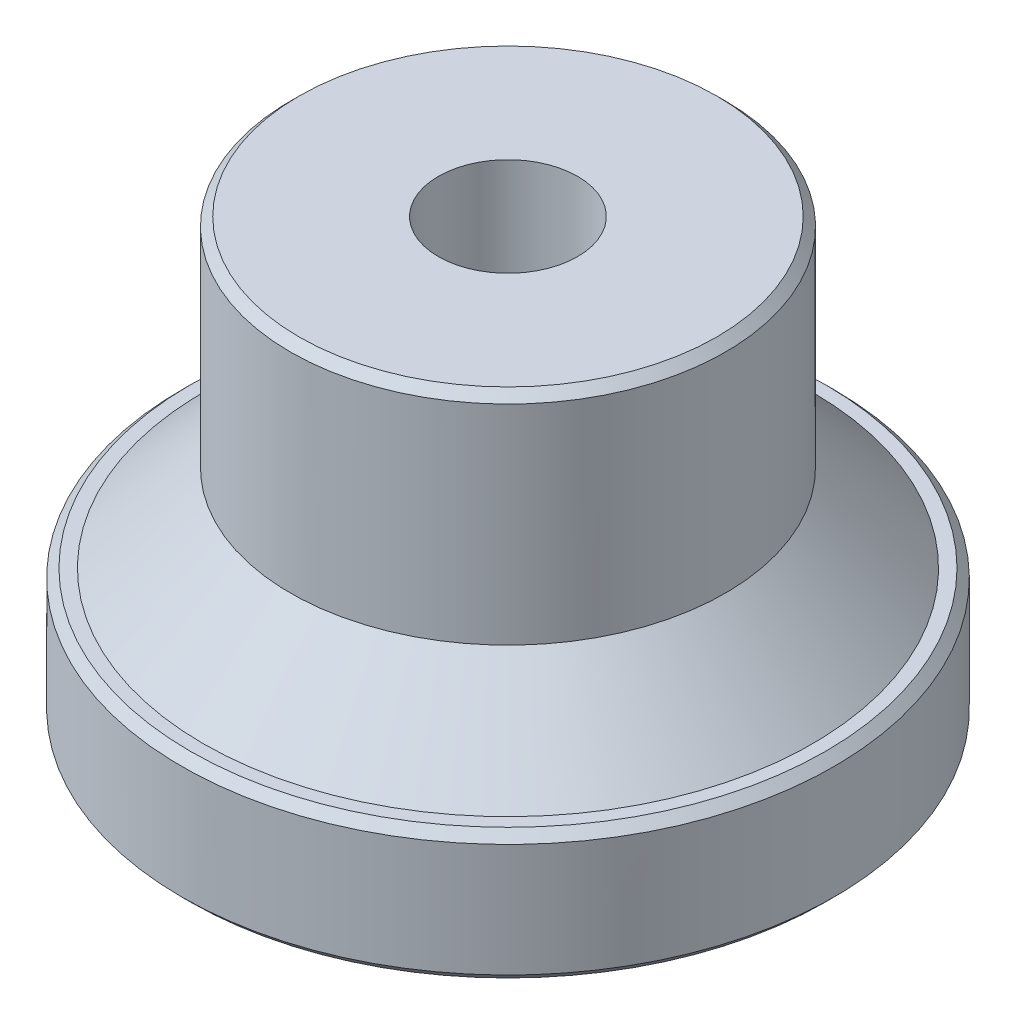
SolidWorks part; units mm, degrees
ref_plane "正面" through (0, 0, 0) normal (0, 0, 1) x (1, 0, 0)
ref_plane "平面" through (0, 0, 0) normal (0, 1, 0) x (1, 0, 0)
ref_plane "右側面" through (0, 0, 0) normal (1, 0, 0) x (0, 0, -1)
sketch "ｽｹｯﾁ1" plane through (0, 0, 0) normal (0, 1, 0) x (1, 0, 0)
  circle A0 centre (0, 0) radius 1.6
  circle A1 centre (0, 0) radius 5
  dimension "D1" = 3.2
  dimension "D2" = 10
extrude "ﾎﾞｽ - 押し出し1" add sketch "ｽｹｯﾁ1" along normal blind 10
sketch "ｽｹｯﾁ2" plane through (0, 0, 0) normal (0, -1, 0) x (1, 0, 0)
  circle A0 centre (0, 0) radius 3
  dimension "D1" = 6
extrude "ｶｯﾄ - 押し出し1" cut sketch "ｽｹｯﾁ2" against normal blind 4
chamfer "面取り1" distance 0.2 angle 45 1 edges at (0, 10, 5)
sketch "ｽｹｯﾁ4" plane through (0, 0, 0) normal (0, -1, 0) x (1, 0, 0)
  circle A0 centre (0, 0) radius 7.5
  circle A1 centre (0, 0) radius 5
  circle A2 centre (0, 0) radius 5 construction
  dimension "D1" = 15
extrude "ﾎﾞｽ - 押し出し2" add sketch "ｽｹｯﾁ4" against normal blind 3
chamfer "面取り2" distance 2 angle 45 1 edges at (0, 3, -5)
chamfer "面取り3" distance 0.2 angle 45 2 edges at (0, 0, -7.5) (0, 3, -7.5)
